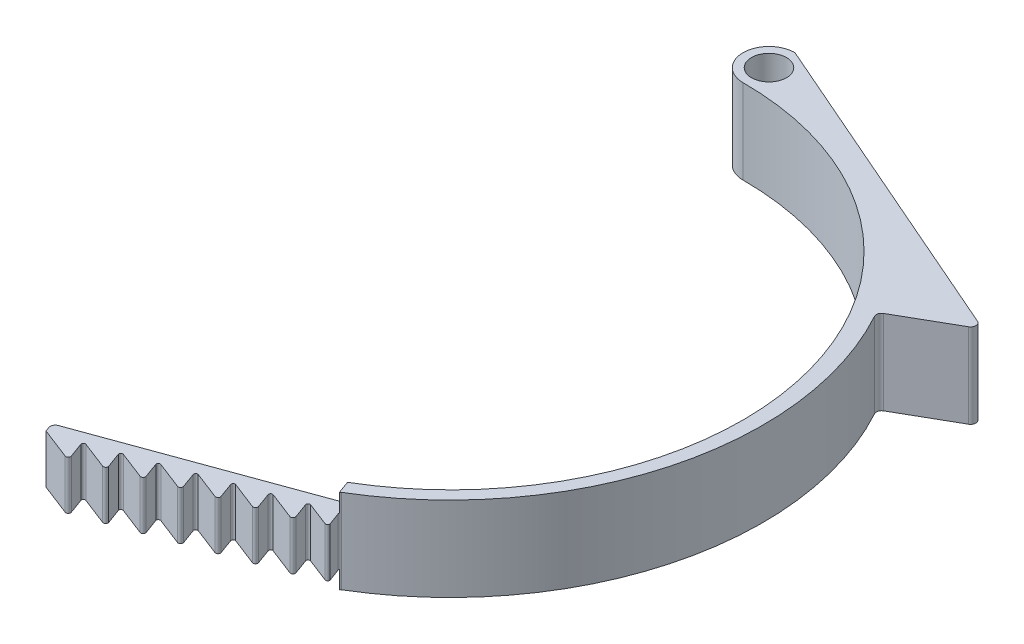
SolidWorks part; units mm, degrees
ref_plane "Front Plane" through (0, 0, 0) normal (0, 0, 1) x (1, 0, 0)
ref_plane "Top Plane" through (0, 0, 0) normal (0, 1, 0) x (1, 0, 0)
ref_plane "Right Plane" through (0, 0, 0) normal (1, 0, 0) x (0, 0, -1)
sketch "Sketch1" plane through (0, 0, 0) normal (0, 1, 0) x (1, 0, 0)
  line L0 (0, 0) -> (22.5, -38.9711) construction
  line L1 (0, 0) -> (0, -45) construction
  line L2 (0, 0) -> (41.4964, -71.8739) construction
  line L3 (0, 53) -> (51.3276, 30.6063)
  line L4 (51.3276, 30.6063) -> (40.9136, 24.6441)
  line L5 (0, 53) -> (0, 49)
  line L7 (0, 49) -> (0, 53)
  line L8 (22.5, -38.9711) -> (-10.4824, -50.9757)
  line L9 (-10.4824, -50.9757) -> (-8.7723, -55.6742)
  line L10 (-8.7723, -55.6742) -> (24.5365, -43.5508)
  line L11 (42.4312, -14.9863) -> (44.3106, -15.6704) construction
  line L13 (24.5365, -43.5508) -> (23.5, -40.7032)
  circle A0 centre (0, 0) radius 45 construction
  arc A1 (0, 45) -> (22.5, -38.9711) centre (0, 0) cw
  arc A2 (0, 45) -> (0, 53) centre (0, 49) cw
  arc A4 (23.5, -40.7032) -> (0, 49) centre (-0.979, 0.8137) ccw
  circle A5 centre (0, 49) radius 2.7
  arc A6 (40.9136, 24.6441) -> (0, 49) centre (-0.979, 0.8137) ccw
  point P9 (-9.6273, -53.325)
  point P14 (51.2922, 30.5253)
  point P19 (51.1447, 30.1917)
  point P20 (40.9136, 24.6441)
  point P21 (-8.4403, -55.1753)
  dimension "D1" = 90
  dimension "D5" = 56
  dimension "D6" = 5.4
  dimension "D2" = 30
  dimension "D3" = 8
  dimension "D4" = 2
  dimension "D7" = 12
  dimension "D8" = 35
  dimension "D9" = 2
  dimension "D10" = 70
  dimension "D11" = 53.363
  dimension "D12" = 5
  dimension "D13" = 20
extrude "Boss-Extrude1" add sketch "Sketch1" along normal blind 13 contours A5 L5 A2 A1 A4 | A5 A4 L4 L3 L5 region at (34.9015, 0, -34.893) region at (-1.2304, 0, -52.35)
sketch "Sketch2" plane through (0, 13, 0) normal (0, 1, 0) x (1, 0, 0)
  line L59 (-8.7723, -55.6742) -> (-9.9693, -52.3853)
  line L60 (-10.4824, -50.9757) -> (-8.7723, -55.6742) construction
  line L61 (-9.9693, -52.3853) -> (-5.0135, -54.3061)
  line L62 (-8.7723, -55.6742) -> (24.5365, -43.5508) construction
  line L63 (-5.0135, -54.3061) -> (-8.7723, -55.6742)
  dimension "D1" = 4
  dimension "D2" = 3.5
extrude "Cut-Extrude3" cut sketch "Sketch2" against normal through all
fillet "Fillet1" radius 0.8 4 edges at (0, 6.5, -53) (51.3276, 6.5, -30.6063) (40.9136, 6.5, -24.6441) (-10.4824, 6.5, 50.9757)
pattern_linear "LPattern1" count 8 spacing 4.5 along (0.9397, 0, -0.342) of "Cut-Extrude3"
fillet "Fillet2" 2 edges at (-5.0135, 6.5, 54.3061) (-4.5437, 6.5, 54.1351) type full round first side face at (-7.4914, 6.5, 53.3457) second side face at (-5.1422, 6.5, 52.4907) middle face at (-4.7786, 6.5, 54.2206)
fillet "Fillet3" 2 edges at (-0.7849, 6.5, 52.767) (-0.315, 6.5, 52.596) type full round first side face at (-3.2628, 6.5, 51.8066) second side face at (-0.9136, 6.5, 50.9516) middle face at (-0.55, 6.5, 52.6815)
fillet "Fillet4" 2 edges at (3.4437, 6.5, 51.2279) (3.9136, 6.5, 51.0569) type full round first side face at (0.9658, 6.5, 50.2675) second side face at (3.315, 6.5, 49.4125) middle face at (3.6786, 6.5, 51.1424)
fillet "Fillet5" 2 edges at (7.6723, 6.5, 49.6889) (8.1422, 6.5, 49.5178) type full round first side face at (5.1944, 6.5, 48.7284) second side face at (7.5437, 6.5, 47.8734) middle face at (7.9073, 6.5, 49.6034)
fillet "Fillet6" 2 edges at (11.901, 6.5, 48.1498) (12.3708, 6.5, 47.9788) type full round first side face at (9.423, 6.5, 47.1893) second side face at (11.7723, 6.5, 46.3343) middle face at (12.1359, 6.5, 48.0643)
fillet "Fillet7" 2 edges at (16.1296, 6.5, 46.6107) (16.5994, 6.5, 46.4397) type full round first side face at (13.6517, 6.5, 45.6503) second side face at (16.0009, 6.5, 44.7952) middle face at (16.3645, 6.5, 46.5252)
fillet "Fillet8" 2 edges at (20.3582, 6.5, 45.0716) (20.828, 6.5, 44.9006) type full round first side face at (17.8803, 6.5, 44.1112) second side face at (20.2295, 6.5, 43.2561) middle face at (20.5931, 6.5, 44.9861)
fillet "Fillet9" radius 0.3 9 edges at (23.5, 6.5, 40.7032) (19.631, 6.5, 41.6117) (15.4024, 6.5, 43.1507) (11.1737, 6.5, 44.6898) (6.9451, 6.5, 46.2289) (2.7165, 6.5, 47.768) (-1.5121, 6.5, 49.3071) (-5.7407, 6.5, 50.8462) (24.5204, 6.5, 43.5068)
sketch "Sketch3" plane through (-25.6395, 0, 9.332) normal (-0.9397, 0, 0.342) x (0.342, 0, 0.9397)
  line L0 (45.1163, 13) -> (45.8163, 13) construction
  line L1 (44.1864, 10.25) -> (50.0968, 10.25)
  line L2 (44.1864, 10.25) -> (44.1864, 2.75)
  line L3 (44.1864, 2.75) -> (50.0968, 2.75)
  line L4 (50.0968, 10.25) -> (50.0968, 2.75)
  dimension "D1" = 7.5
  dimension "D2" = 2.75
extrude "Cut-Extrude2" cut sketch "Sketch3" against normal blind 35.5 flip side to cut
